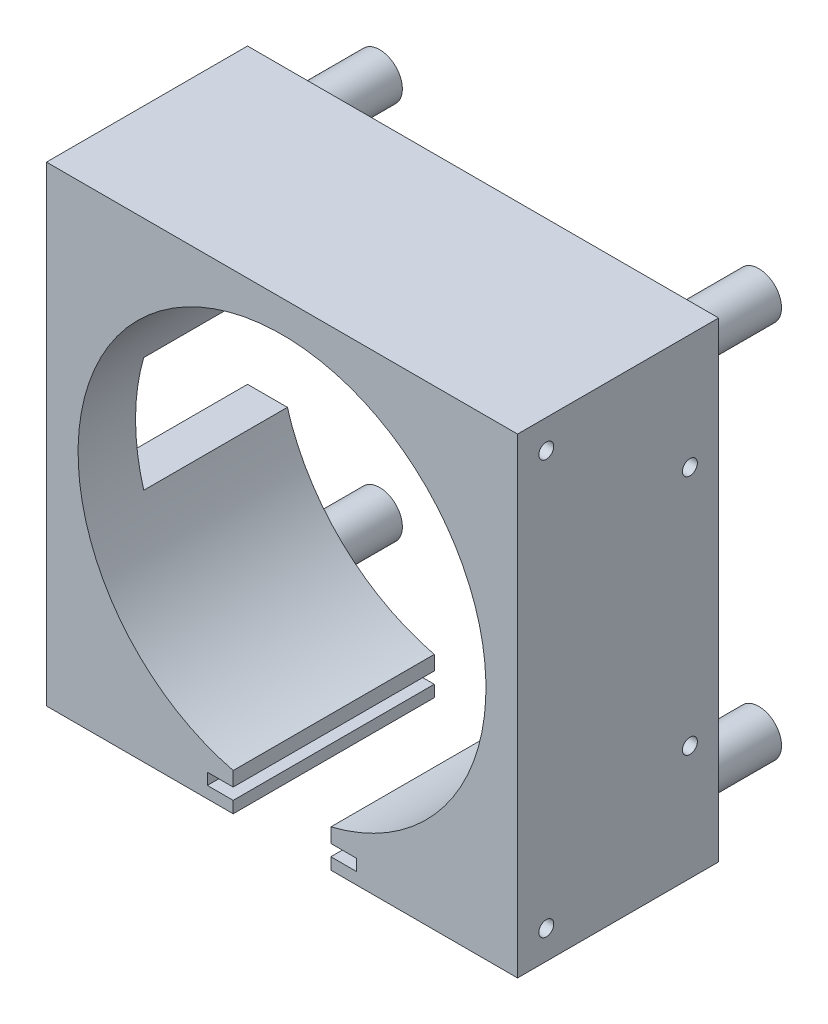
SolidWorks part; units mm, degrees
ref_plane "前基準面" through (0, 0, 0) normal (0, 0, 1) x (1, 0, 0)
ref_plane "上基準面" through (0, 0, 0) normal (0, 1, 0) x (1, 0, 0)
ref_plane "右基準面" through (0, 0, 0) normal (1, 0, 0) x (0, 0, -1)
ref_axis "基準軸1" through (0, -55, 0) along (0, 1, 0)
ref_axis "基準軸2" through (-88.99, 0, 0) along (1, 0, 0)
ref_axis "基準軸3" through (0, 0, 55) along (0, 0, -1)
sketch "草圖1" plane through (0, 0, 0) normal (0, 0, 1) x (1, 0, 0)
  line L0 (-88.99, 0) -> (88.99, 0) construction
  line L1 (-41, -41) -> (41, -41)
  line L2 (-41, -41) -> (-41, 41)
  line L3 (-41, 41) -> (41, 41)
  line L4 (41, -41) -> (41, 41)
  line L5 (0, -55) -> (0, 55) construction
  circle A0 centre (0, 0) radius 35.5
  point P6 (-41, 0)
  point P12 (0, 41)
  dimension "D1" = 71
  dimension "D2" = 82
  dimension "D3" = 82
extrude "填料-伸長1" add sketch "草圖1" along normal blind 35
sketch "草圖2" plane through (0, 0, 35) normal (0, 0, 1) x (1, 0, 0)
  line L0 (-41, 41) -> (-41, -41) construction
  line L1 (-41, 10) -> (-33, 10)
  line L2 (-41, 10) -> (-41, -10)
  line L3 (-41, -10) -> (-33, -10)
  line L4 (-33, 10) -> (-33, -10)
  line L7 (55, 0) -> (-55, 0) construction
  point P8 (-33, 0)
  dimension "D1" = 8
  dimension "D2" = 20
  dimension "D3" = 0
extrude "除料-伸長1" cut sketch "草圖2" against normal up to next from offset 10 offset against normal yes
sketch "草圖3" plane through (0, 0, 0) normal (0, 0, -1) x (-1, 0, 0)
  line L0 (41, 41) -> (41, 10) construction
  line L1 (-41, 41) -> (41, 41) construction
  circle A0 centre (33, 33) radius 3.95
  dimension "D1" = 7.9
  dimension "D2" = 8
  dimension "D3" = 8
extrude "填料-伸長2" add sketch "草圖3" along normal blind 15
pattern_circular "環狀複製排列1" count 4 over 360 about axis through (0, 0, 55) along (0, 0, -1) of "填料-伸長2"
sketch "草圖4" plane through (-41, 0, 0) normal (-1, 0, 0) x (0, 0, 1)
  line L0 (0, -55) -> (0, 55) construction
  line L1 (35, -41) -> (0, -41) construction
  line L2 (35, 41) -> (35, -41) construction
  circle A0 centre (5, -21) radius 1.3
  circle A1 centre (30, -36) radius 1.3
  dimension "D1" = 2.6
  dimension "D4" = 2.6
  dimension "D2" = 5
  dimension "D3" = 20
  dimension "D5" = 5
  dimension "D6" = 5
extrude "除料-伸長2" cut sketch "草圖4" against normal blind 9
mirror "鏡射2" about plane through (0, 0, 0) normal (0, 1, 0) of "除料-伸長2"
mirror "鏡射4" about plane through (0, 0, 0) normal (1, 0, 0) of "鏡射2"
sketch "草圖5" plane through (0, 0, 35) normal (0, 0, 1) x (1, 0, 0)
  line L0 (-8.5, -36.9674) -> (-8.5, -34.4674)
  line L1 (-8.5, -41.4674) -> (8.5, -41.4674)
  line L2 (-8.5, -41.4674) -> (-8.5, -38.9674)
  line L3 (-8.5, -34.4674) -> (8.5, -34.4674)
  line L4 (8.5, -41.4674) -> (8.5, -38.9674)
  line L5 (8.5, -38.9674) -> (13, -38.9674)
  line L7 (8.5, -36.9674) -> (13, -36.9674)
  line L8 (13, -38.9674) -> (13, -36.9674)
  line L9 (-8.5, -38.9674) -> (-13, -38.9674)
  line L11 (-8.5, -36.9674) -> (-13, -36.9674)
  line L12 (-13, -38.9674) -> (-13, -36.9674)
  line L13 (8.5, -36.9674) -> (8.5, -34.4674)
  circle A0 centre (0, 0) radius 35.5 construction
  dimension "D1" = 17
  dimension "D2" = 7
  dimension "D3" = 2.5
  dimension "D4" = 2
  dimension "D5" = 4.5
  dimension "D6" = 2
  dimension "D7" = 2.5
  dimension "D8" = 4.5
extrude "除料-伸長3" cut sketch "草圖5" against normal through all
